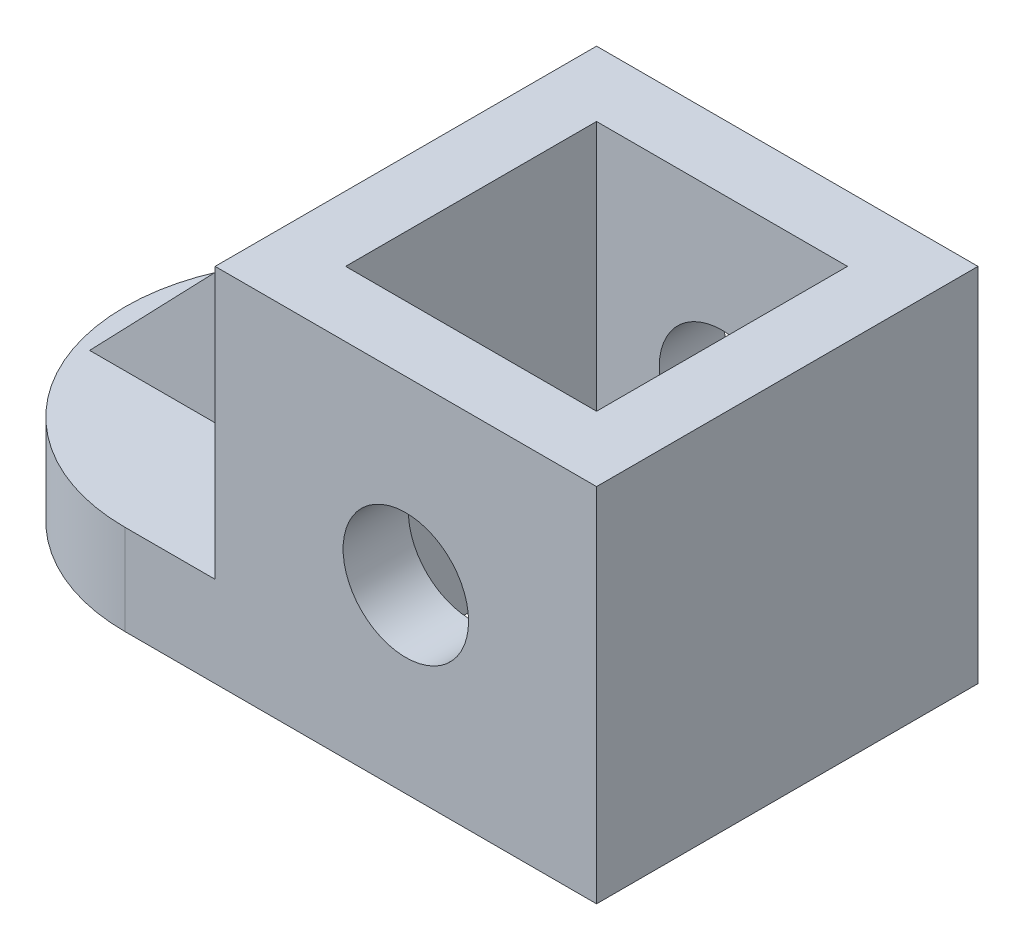
SolidWorks part; units mm, degrees
ref_plane "Ön Düzlem" through (0, 0, 0) normal (0, 0, 1) x (1, 0, 0)
ref_plane "Üst Düzlem" through (0, 0, 0) normal (0, 1, 0) x (1, 0, 0)
ref_plane "Sağ Düzlem" through (0, 0, 0) normal (1, 0, 0) x (0, 0, -1)
sketch "Çizim8" plane through (0, 0, 0) normal (0, 0, 1) x (1, 0, 0)
  line L1 (-185.9341, 55.9356) -> (-109.9341, 55.9356)
  line L2 (-185.9341, 55.9356) -> (-185.9341, 1.9356)
  line L4 (-109.9341, 55.9356) -> (-109.9341, -16.0644)
  line L5 (-109.9341, -16.0644) -> (-241.9341, -16.0644)
  line L7 (-185.9341, 1.9356) -> (-241.9341, 1.9356)
  line L8 (-241.9341, -16.0644) -> (-241.9341, 1.9356)
  dimension "D1" = 76
  dimension "D2" = 72
  dimension "D3" = 132
  dimension "D4" = 18
extrude "Yükseklik-Ekstrüzyon3" add sketch "Çizim8" along normal blind 76
sketch "Çizim9" plane through (0, 55.9356, 0) normal (0, 1, 0) x (1, 0, 0)
  line L0 (-109.9341, -76) -> (-185.9341, -76) construction
  line L1 (-172.9341, -13) -> (-122.9341, -13)
  line L2 (-172.9341, -13) -> (-172.9341, -63)
  line L3 (-172.9341, -63) -> (-122.9341, -63)
  line L4 (-122.9341, -13) -> (-122.9341, -63)
  line L5 (-185.9341, -76) -> (-185.9341, 0) construction
  dimension "D1" = 50
  dimension "D2" = 50
  dimension "D3" = 13
  dimension "D4" = 13
extrude "Kes-Ekstrüzyon2" cut sketch "Çizim9" against normal blind 72
fillet "Radyus2" 2 edges at (-241.9341, -7.0644, 76) (-241.9341, -7.0644, 0) type full round first side face at (-179.2674, 13.9356, 76) second side face at (-179.2674, 13.9356, 0) middle face at (-241.9341, -7.0644, 38)
sketch "Çizim10" plane through (0, 0, 76) normal (0, 0, 1) x (1, 0, 0)
  line L0 (-109.9341, 55.9356) -> (-185.9341, 55.9356) construction
  line L1 (-109.9341, -16.0644) -> (-109.9341, 55.9356) construction
  circle A0 centre (-147.9341, 19.9356) radius 12.5
  dimension "D1" = 25
  dimension "D2" = 36
  dimension "D3" = 38
extrude "Kes-Ekstrüzyon3" cut sketch "Çizim10" against normal through all contours A0
ref_plane "Düzlem1" through (0, 0, 38) normal (0, 0, 1) x (1, 0, 0)
sketch "Çizim11" plane through (0, 0, 38) normal (0, 0, 1) x (1, 0, 0)
  line L0 (-185.9341, 55.9356) -> (-237.9341, 1.9356)
  line L1 (-203.9341, 1.9356) -> (-241.9341, 1.9356) construction
  dimension "D1" = 4
rib "Feder1" sketch "Çizim11" sketch "Çizim11" thickness 22 extrusion direction parallel to sketch draft on no parameters "D1"=22
